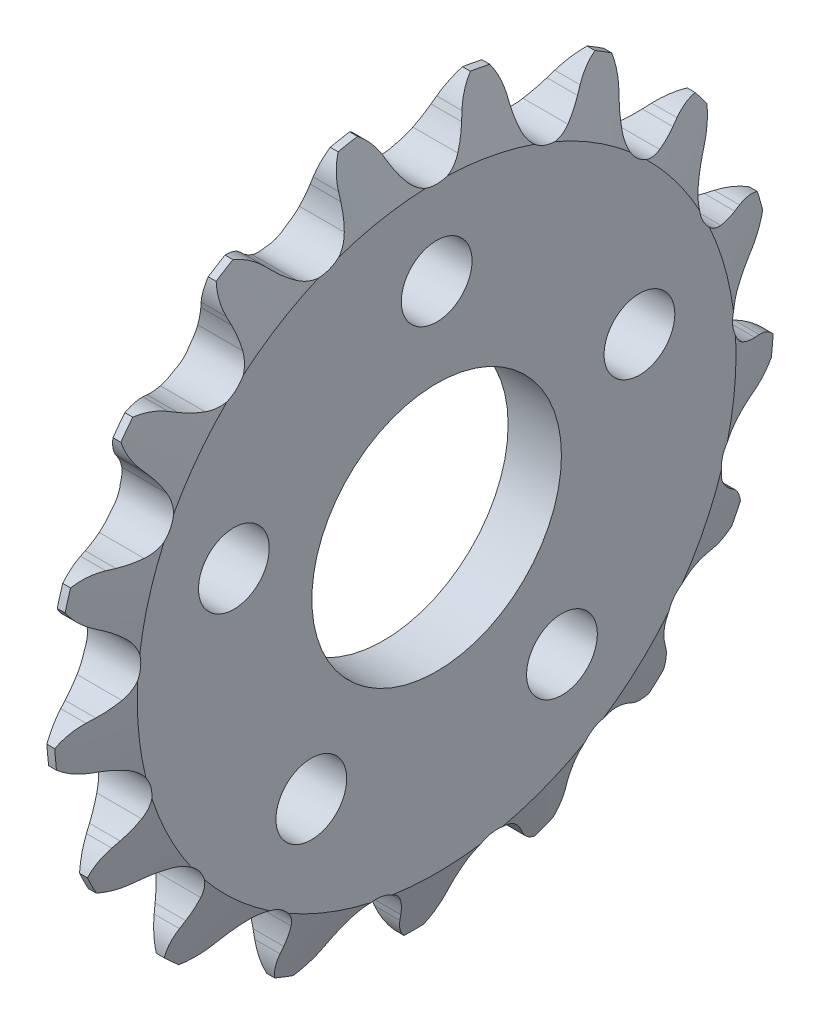
SolidWorks part; units mm, degrees
material "Alloy Steel"
ref_plane "Front Plane" through (0, 0, 0) normal (0, 0, 1) x (1, 0, 0)
ref_plane "Top Plane" through (0, 0, 0) normal (0, 1, 0) x (1, 0, 0)
ref_plane "Right Plane" through (0, 0, 0) normal (1, 0, 0) x (0, 0, -1)
ref_axis "X AXIS" through (-88.99, 0, 0) along (1, 0, 0)
ref_axis "Y AXIS" through (0, -55, 0) along (0, 1, 0)
ref_axis "Z AXIS" through (0, 0, 55) along (0, 0, -1)
other "Freeze***"
sketch "Sketch1" plane through (0, 0, 0) normal (1, 0, 0) x (0, 0, -1)
  line L0 (0, 17.279) -> (-6.2419, 16.1121) construction
  line L1 (-1.9028, 17.1719) -> (-2.0594, 17.5266)
  line L2 (-1.9028, 17.1719) -> (2.0665, 18.9245) construction
  line L3 (2.0665, 18.9245) -> (0, 17.279) construction
  line L4 (0, 17.279) -> (-1.95, 17.279) construction
  line L5 (-3.5432, 18.9545) -> (-3.1209, 16.6956) construction
  line L6 (0, 17.279) -> (0, 15.5816) construction
  circle A0 centre (0, 0) radius 17.279 construction
  arc A1 (-1.3278, 16.2216) -> (0, 15.5816) centre (0, 17.279) ccw
  arc A2 (-1.3278, 16.2216) -> (-1.9028, 17.1719) centre (2.0665, 18.9245) cw
  arc A3 (-2.0594, 17.5266) -> (-3.5432, 18.9545) centre (-4.5441, 16.4295) ccw
sketch "Sketch2" plane through (0, 0, 0) normal (0, 0, 1) x (1, 0, 0)
  line L0 (0, 0) -> (0, 18.8665) construction
  line L1 (-0.2064, 18.8665) -> (0.2064, 18.8665)
  line L2 (0.2064, 18.8665) -> (1.397, 15.6915)
  line L3 (1.397, 15.6915) -> (1.397, 0)
  line L4 (-1.397, 0) -> (1.397, 0)
  line L5 (-1.397, 15.6915) -> (-1.397, 0)
  line L6 (-0.2064, 18.8665) -> (-1.397, 15.6915)
  dimension "D1" = 18.8665
  dimension "D2" = 2.794
revolve "Revolve1" add sketch "Sketch2" angle 360 about L4
sketch "Sketch3" plane through (0, 0, 0) normal (1, 0, 0) x (0, 0, -1)
  line L0 (-1.9028, 17.1719) -> (-2.0594, 17.5266) construction
  line L1 (-1.9028, 17.1719) -> (-2.0594, 17.5266)
  line L2 (0, 15.5816) -> (0, 0) construction
  line L3 (1.9028, 17.1719) -> (2.0594, 17.5266)
  arc A0 (-2.0594, 17.5266) -> (-3.5432, 18.9545) centre (-4.5441, 16.4295) ccw construction
  arc A1 (-1.9028, 17.1719) -> (-1.3278, 16.2216) centre (2.0665, 18.9245) ccw construction
  arc A2 (-1.3278, 16.2216) -> (0, 15.5816) centre (0, 17.279) ccw construction
  arc A3 (-2.0594, 17.5266) -> (-3.5432, 18.9545) centre (-4.5441, 16.4295) ccw
  arc A4 (-1.9028, 17.1719) -> (-1.3278, 16.2216) centre (2.0665, 18.9245) ccw
  arc A5 (-1.3278, 16.2216) -> (1.3278, 16.2216) centre (0, 17.279) ccw
  arc A6 (1.9028, 17.1719) -> (1.3278, 16.2216) centre (-2.0665, 18.9245) cw
  arc A7 (2.0594, 17.5266) -> (3.5432, 18.9545) centre (4.5441, 16.4295) cw
  arc A8 (-3.5432, 18.9545) -> (3.5432, 18.9545) centre (0, 0) cw
extrude "Cut-Extrude1" cut sketch "Sketch3" against normal through all both and the other way through all contours A8 A3 L1 A4 A5 A6 L3 A7 region at (0, 17.7714, 0)
pattern_circular "CirPattern1" count 17 over 360 about axis through (-88.99, 0, 0) along (1, 0, 0) of "Cut-Extrude1"
sketch "Sketch4" plane through (1.397, 0, 0) normal (1, 0, 0) x (0, 0, -1)
  line L0 (0, 0) -> (0, 11.176) construction
  circle A0 centre (0, 0) radius 6.5405
  circle A1 centre (0, 11.176) radius 1.8542
  circle A2 centre (10.629, 3.4536) radius 1.8542
  circle A3 centre (6.5691, -9.0416) radius 1.8542
  circle A4 centre (-6.5691, -9.0416) radius 1.8542
  circle A5 centre (-10.629, 3.4536) radius 1.8542
  point P15 (0, 0)
  dimension "D1" = 13.081
  dimension "D2" = 5
  dimension "D3" = 3.7084
  dimension "D4" = 11.176
extrude "Cut-Extrude2" cut sketch "Sketch4" against normal through all
equation "\"p\"= 2 / 8"
equation "\"n\"= 17"
equation "\"Dr\"= 0.13"
equation "\"Ds\"= 1.005 * \"Dr\" + 0.003"
equation "\"PD\"= \"p\" * cosec ( 180 / \"n\" )"
equation "\"A\"= 35 + 60 / \"n\""
equation "\"B\"= 18 - 56 / \"n\""
equation "\"ac\"= 0.8 * \"Dr\""
equation "\"ab\"= 1.4 * \"Dr\""
equation "\"D1@Sketch1\"=\"PD\""
equation "\"D2@Sketch1\"=\"p\""
equation "\"D3@Sketch1\"=\"Ds\""
equation "\"D4@Sketch1\"=\"A\""
equation "\"D5@Sketch1\"=\"B\""
equation "\"D6@Sketch1\"=\"ac\""
equation "\"D7@Sketch1\"=\"ab\""
equation "\"D1@Sketch2\"=(\"PD\"+\"p\"/2)/2"
equation "\"D4@Sketch2\"=\"p\"/2"
equation "\"D1@CirPattern1\"=\"n\""
